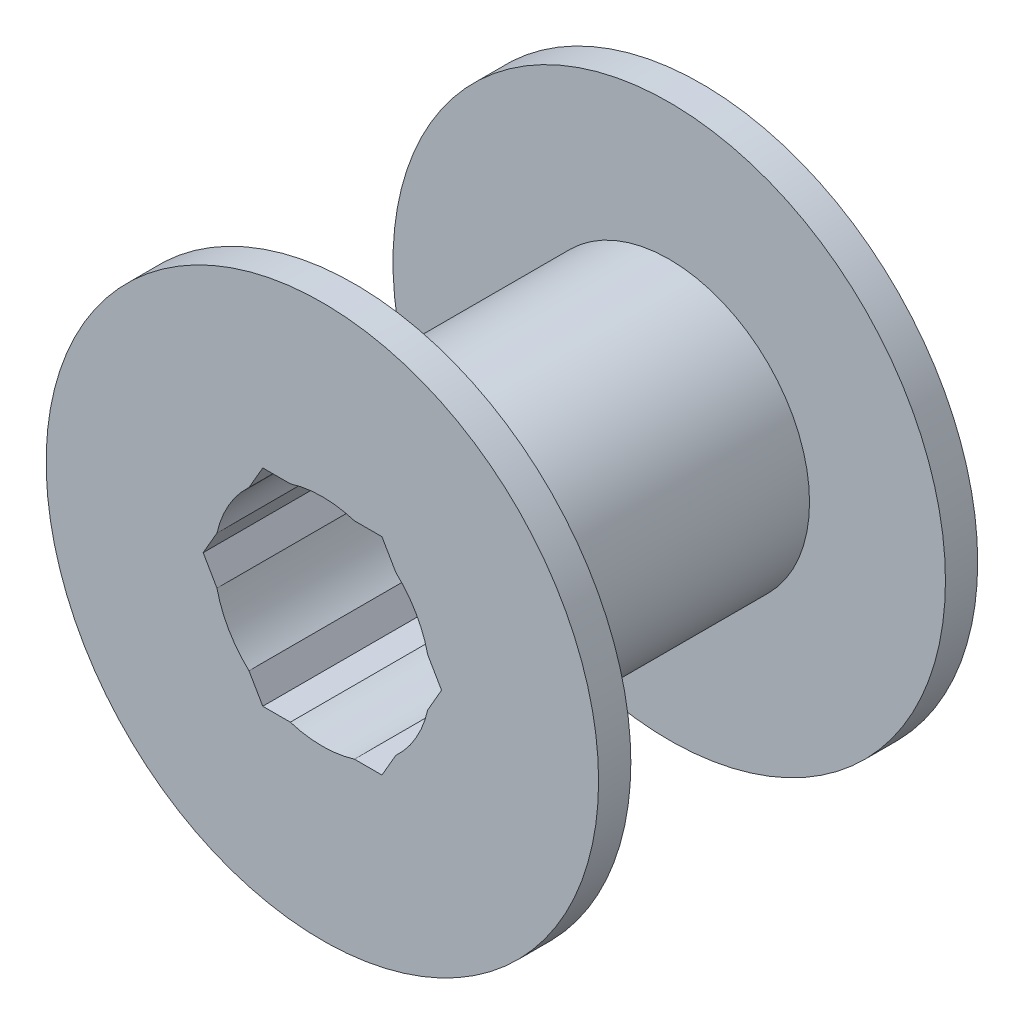
SolidWorks part; units mm, degrees
material "UNOBTANIUM"
ref_plane "Top Plane" through (0, 0, 0) normal (0, 0, 1) x (1, 0, 0)
ref_plane "Right Plane" through (0, 0, 0) normal (0, 1, 0) x (1, 0, 0)
ref_plane "Front Plane" through (0, 0, 0) normal (1, 0, 0) x (0, 0, -1)
ref_axis "x-axis" through (-88.99, 0, 0) along (1, 0, 0)
ref_axis "y-axis" through (0, -55, 0) along (0, 1, 0)
ref_axis "z-axis" through (0, 0, 55) along (0, 0, -1)
sketch "Sketch1" plane through (0, 0, 0) normal (1, 0, 0) x (0, 0, -1)
  line L0 (-13.61, 23.9) -> (-13.61, 12.14)
  line L1 (-13.61, 12.14) -> (13.61, 12.14)
  line L2 (13.61, 12.14) -> (13.61, 23.9)
  line L3 (13.61, 23.9) -> (16.4, 23.9)
  line L4 (16.4, 23.9) -> (16.4, 9.35)
  line L5 (16.4, 9.35) -> (-16.4, 9.35)
  line L6 (-16.4, 9.35) -> (-16.4, 23.9)
  line L7 (-16.4, 23.9) -> (-13.61, 23.9)
  line L8 (-33.4489, 0) -> (51.5331, 0) construction
  line L9 (0, 9.35) -> (0, 0) construction
  line L10 (0, 12.14) -> (0, 9.35) construction
  point P14 (13.61, 32.0212)
  dimension "D1" = 18.7
  dimension "D2" = 32.8
  dimension "D3" = 2.79
  dimension "D4" = 47.8
revolve "Revolve1" add sketch "Sketch1" angle 360 about L8
sketch "Sketch2" plane through (0, 0, 16.4) normal (0, 0, 1) x (1, 0, 0)
  line L1 (5.1557, 8.93) -> (-5.1557, 8.93)
  line L2 (-5.1557, 8.93) -> (-10.3115, 0)
  line L3 (-10.3115, 0) -> (-5.1557, -8.93)
  line L4 (-5.1557, -8.93) -> (5.1557, -8.93)
  line L5 (5.1557, -8.93) -> (10.3115, 0)
  line L6 (10.3115, 0) -> (5.1557, 8.93)
  circle A0 centre (0, 0) radius 8.93 construction
  dimension "D1" = 17.86
extrude "Cut-Extrude1" cut sketch "Sketch2" against normal through all
